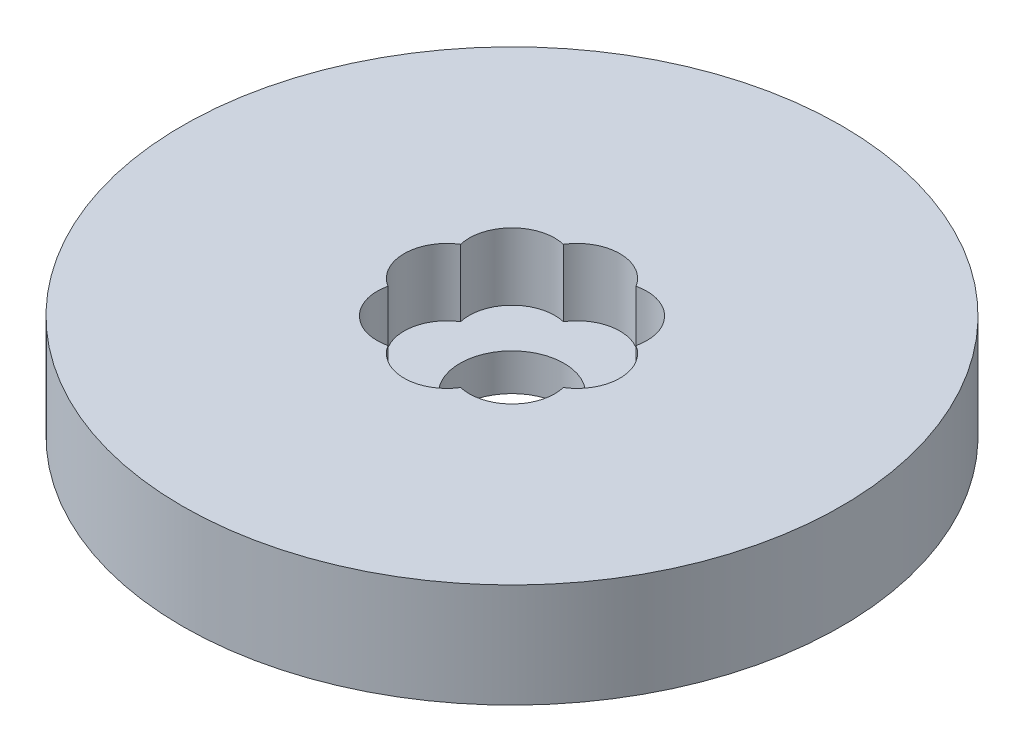
SolidWorks part; units mm, degrees
ref_plane "Front Plane" through (0, 0, 0) normal (0, 0, 1) x (1, 0, 0)
ref_plane "Top Plane" through (0, 0, 0) normal (0, 1, 0) x (1, 0, 0)
ref_plane "Right Plane" through (0, 0, 0) normal (1, 0, 0) x (0, 0, -1)
sketch "Sketch1" plane through (0, 0, 0) normal (0, 1, 0) x (1, 0, 0)
  circle A0 centre (0, 0) radius 47.5
  dimension "FLANGE_OD" = 95
extrude "Boss-Extrude1" add sketch "Sketch1" along normal blind 15
sketch "Sketch2" plane through (0, 0, 0) normal (0, 1, 0) x (1, 0, 0)
  circle A0 centre (0, 0) radius 7.5
  dimension "BORE_D" = 15
extrude "Cut-Extrude1" cut sketch "Sketch2" along normal through all
sketch "Sketch3" plane through (0, 15, 0) normal (0, 1, 0) x (1, 0, 0)
  circle A0 centre (0, 0) radius 9.3906 construction
  circle A1 centre (-9.3906, 0) radius 6.1636
  dimension "BOLT_D" = 12.3272
  dimension "BOLT_PCD" = 18.7813
extrude "Cut-Extrude2" cut sketch "Sketch3" against normal blind 9.6615
pattern_circular "CirPattern1" count 8 over 360 about axis through (0, 0, 0) along (0, 1, 0) of "Cut-Extrude2"
